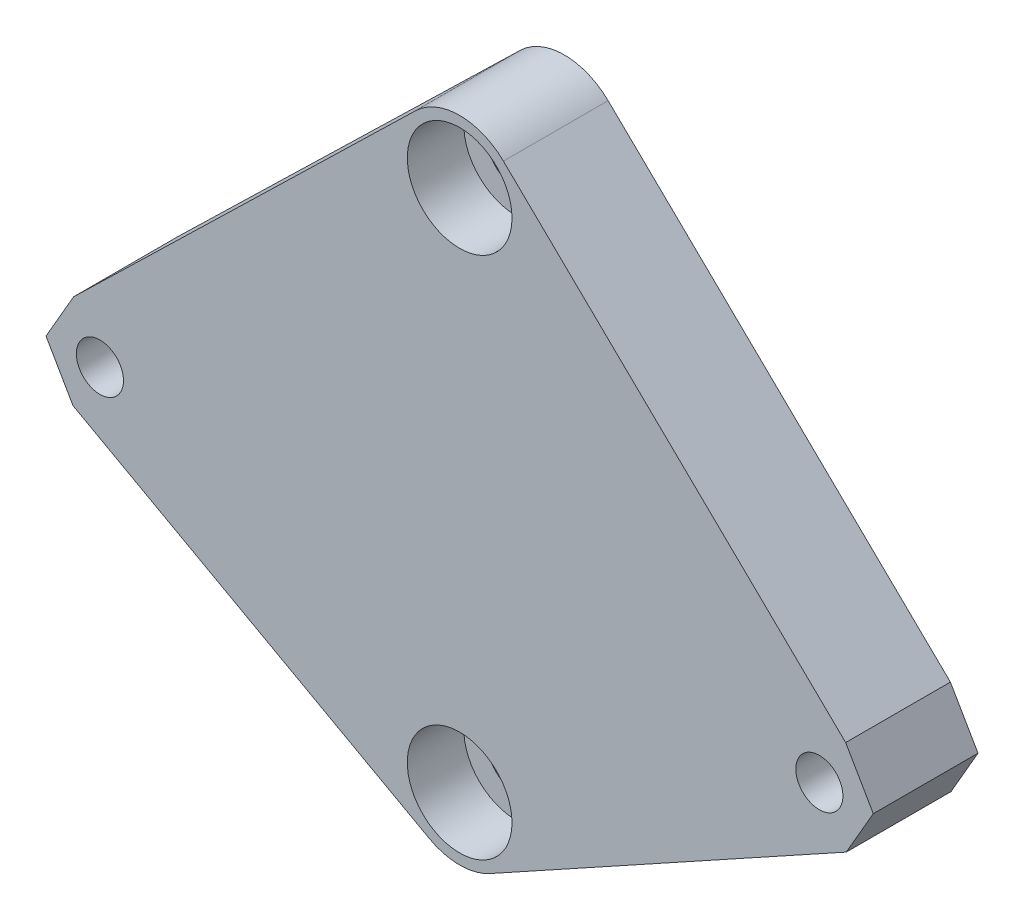
SolidWorks part; units mm, degrees
ref_plane "Top" through (0, 0, 0) normal (0, 0, 1) x (1, 0, 0)
ref_plane "Front" through (0, 0, 0) normal (0, 1, 0) x (1, 0, 0)
ref_plane "Right" through (0, 0, 0) normal (1, 0, 0) x (0, 0, -1)
sketch "Sketch1" plane through (0, 0, 0) normal (0, 0, 1) x (1, 0, 0)
  line L1 (0, 0) -> (79, 0)
  line L2 (0, 0) -> (0, 70)
  line L3 (0, 70) -> (79, 70)
  line L4 (79, 0) -> (79, 70)
  dimension "D1" = 79
  dimension "D2" = 70
extrude "Boss-Extrude1" add sketch "Sketch1" along normal blind 10
sketch "Sketch4" plane through (0, 0, 10) normal (0, 0, 1) x (1, 0, 0)
  line L0 (5.15, 28) -> (73.85, 28)
  line L2 (79, 0) -> (79, 70) construction
  line L5 (79, 70) -> (0, 70) construction
  point P2 (39.5, 28)
  dimension "D1" = 68.7
  dimension "D2" = 39.5
  dimension "D3" = 42
hole_wizard "M4 Clearance Hole1" positions "Sketch5" profile "Sketch6" hole size "M4" standard "DIN" end condition through all
sketch "Sketch5" plane through (0, 0, 10) normal (0, 0, 1) x (1, 0, 0)
  point P0 (5.15, 28)
  point P3 (73.85, 28)
sketch "Sketch6" plane through (5.15, 28, 10) normal (1, 0, 0) x (0, -1, 0)
  line L0 (0, 0) -> (0, 10)
  line L1 (0, 10) -> (2.25, 10)
  line L2 (2.25, 10) -> (2.25, 0)
  line L5 (2.25, 0) -> (0, 0)
  line L11 (0, -6.35) -> (0, 107.95) construction
  dimension "Thru Hole Dia." = 4.5
  dimension "Thru Hole Depth" = 10
sketch "Sketch11" plane through (0, 0, 0) normal (0, 0, -1) x (-1, 0, 0)
  line L0 (-79, 70) -> (0, 70) construction
  line L1 (-69.6353, 28) -> (-71.7427, 31.65)
  line L2 (-71.7427, 31.65) -> (-75.9573, 31.65)
  line L3 (-75.9573, 31.65) -> (-78.0647, 28)
  line L4 (-78.0647, 28) -> (-75.9573, 24.35)
  line L5 (-75.9573, 24.35) -> (-71.7427, 24.35)
  line L6 (-71.7427, 24.35) -> (-69.6353, 28)
  line L7 (-9.3647, 28) -> (-7.2573, 24.35)
  line L8 (-7.2573, 24.35) -> (-3.0427, 24.35)
  line L9 (-3.0427, 24.35) -> (-0.9353, 28)
  line L10 (-0.9353, 28) -> (-3.0427, 31.65)
  line L11 (-3.0427, 31.65) -> (-7.2573, 31.65)
  line L12 (-7.2573, 31.65) -> (-9.3647, 28)
  circle A0 centre (-73.85, 28) radius 3.65 construction
  circle A1 centre (-5.15, 28) radius 3.65 construction
  dimension "D1" = 7.3
  dimension "D2" = 7.3
extrude "Cut-Extrude3" cut sketch "Sketch11" against normal blind 3.5
sketch "Sketch12" plane through (0, 0, 10) normal (0, 0, -1) x (-1, 0, 0)
  line L0 (-39.5, 60) -> (-39.5, 10)
  line L1 (-79, 0) -> (-79, 70) construction
  line L2 (0, 0) -> (-79, 0) construction
  dimension "D1" = 39.5
  dimension "D2" = 50
  dimension "D3" = 10
hole_wizard "CBORE for M5 Socket Head Cap Screw1" positions "Sketch15" profile "Sketch16" counterbore size "M5" standard "DIN" end condition through all
sketch "Sketch15" plane through (0, 0, 10) normal (0, 0, 1) x (1, 0, 0)
  point P0 (39.5, 60)
  point P3 (39.5, 10)
sketch "Sketch16" plane through (39.5, 60, 10) normal (1, 0, 0) x (0, -1, 0)
  line L0 (0, 0) -> (0, 10)
  line L1 (0, 10) -> (2.75, 10)
  line L3 (2.75, 10) -> (2.75, 5.4)
  line L4 (2.75, 5.4) -> (5, 5.4)
  line L5 (5, 5.4) -> (5, 0)
  line L7 (5, 0) -> (0, 0)
  line L11 (0, -6.35) -> (0, 107.95) construction
  dimension "Thru Hole Dia." = 5.5
  dimension "Thru Hole Depth" = 10
  dimension "C'Bore Dia." = 10
  dimension "C'Bore Depth" = 5.4
sketch "Sketch17" plane through (0, 0, 0) normal (0, 0, -1) x (-1, 0, 0)
  line L0 (-76.3644, 32.565) -> (-43.68, 64.3044)
  line L2 (-35.32, 64.3044) -> (-2.6356, 32.565)
  line L4 (-76.4203, 23.5319) -> (-42.4002, 4.7475)
  line L5 (-36.5998, 4.7475) -> (-2.5797, 23.5319)
  line L14 (-2.5797, 23.5319) -> (0, 28)
  line L15 (0, 70) -> (0, 0) construction
  line L16 (0, 28) -> (-2.6356, 32.565)
  line L17 (-0.9353, 28) -> (-3.0427, 31.65) construction
  line L18 (-3.0427, 24.35) -> (-0.9353, 28) construction
  line L20 (-76.3644, 32.565) -> (-79, 28)
  line L21 (-79, 0) -> (-79, 70) construction
  line L22 (-79, 28) -> (-76.4203, 23.5319)
  line L23 (-78.0647, 28) -> (-75.9573, 24.35) construction
  line L24 (-75.9573, 31.65) -> (-78.0647, 28) construction
  line L25 (-125.188, 28) -> (-105.4971, -6.1057)
  line L26 (-105.4971, -6.1057) -> (-61.7349, -30.2692)
  line L27 (-17.2651, -30.2692) -> (26.4971, -6.1057)
  line L28 (26.4971, -6.1057) -> (46.188, 28)
  line L29 (46.188, 28) -> (29.223, 57.3843)
  line L30 (-7.4537, 93.0005) -> (29.223, 57.3843)
  line L31 (-108.223, 57.3843) -> (-71.5463, 93.0005)
  line L32 (-108.223, 57.3843) -> (-125.188, 28)
  arc A0 (-43.68, 64.3044) -> (-35.32, 64.3044) centre (-39.5, 60) cw
  arc A1 (-42.4002, 4.7475) -> (-36.5998, 4.7475) centre (-39.5, 10) ccw
  arc A4 (-61.7349, -30.2692) -> (-17.2651, -30.2692) centre (-39.5, 10) ccw
  arc A5 (-71.5463, 93.0005) -> (-7.4537, 93.0005) centre (-39.5, 60) cw
  point P24 (0, 0)
  dimension "D2" = 6
  dimension "D4" = 6
  dimension "D1" = 0.94
  dimension "D3" = 0.94
  dimension "D5" = 0.94
  dimension "D6" = 0.94
  dimension "D7" = 40
extrude "Cut-Extrude4" cut sketch "Sketch17" against normal blind 10
